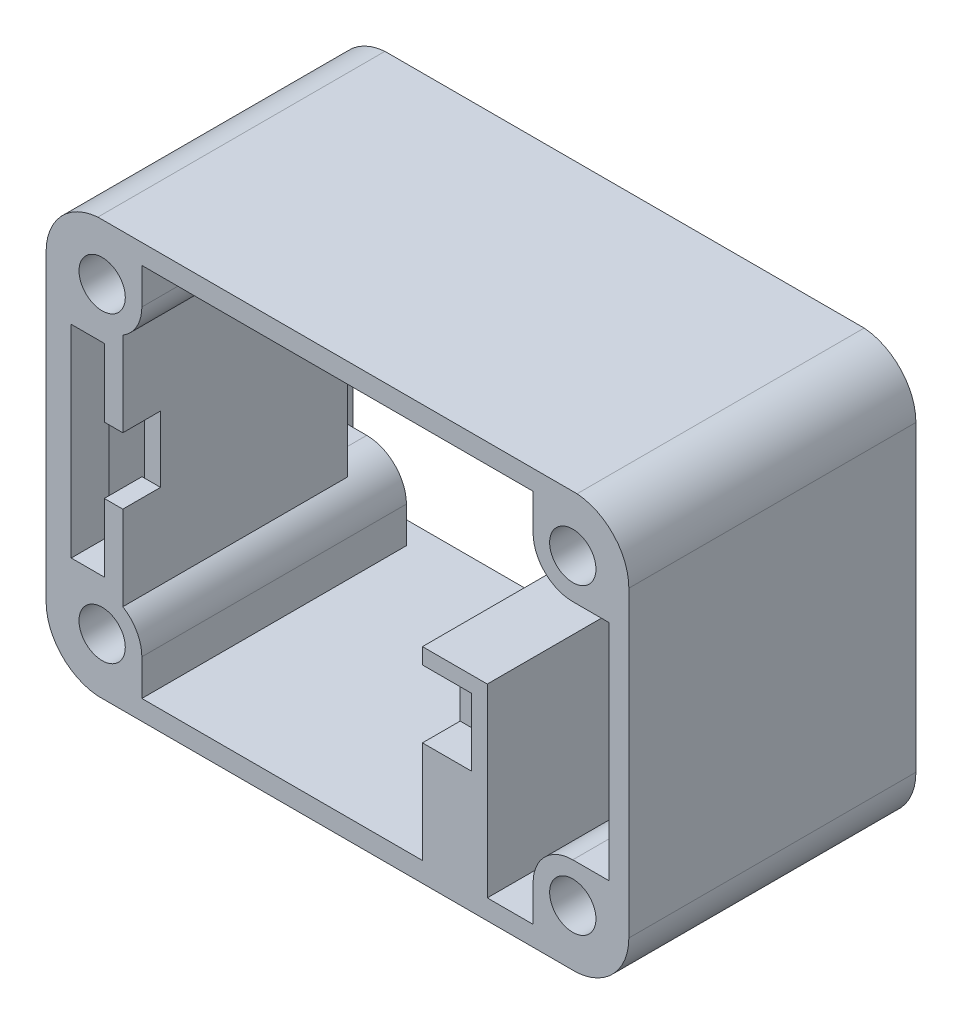
SolidWorks part; units mm, degrees
ref_plane "Front Plane" through (0, 0, 0) normal (0, 0, 1) x (1, 0, 0)
ref_plane "Top Plane" through (0, 0, 0) normal (0, 1, 0) x (1, 0, 0)
ref_plane "Right Plane" through (0, 0, 0) normal (1, 0, 0) x (0, 0, -1)
sketch "Sketch1" plane through (0, 0, 0) normal (0, 0, 1) x (1, 0, 0)
  line L0 (-20.325, 13.975) -> (-20.325, 14.175) construction
  line L1 (-22.025, -15.675) -> (22.025, -15.675)
  line L2 (-22.025, -15.675) -> (-22.025, 15.675)
  line L3 (-22.025, 15.675) -> (22.025, 15.675)
  line L4 (20.325, -13.975) -> (20.325, 13.975)
  line L5 (20.325, 13.975) -> (-20.325, 13.975)
  line L6 (-20.325, 13.975) -> (-20.325, -13.975)
  line L7 (-20.325, -13.975) -> (20.325, -13.975)
  line L8 (20.325, -13.975) -> (20.325, 13.975)
  line L9 (20.325, 13.975) -> (-20.325, 13.975)
  line L10 (-20.325, 13.975) -> (-20.325, -13.975)
  line L11 (-20.325, -13.975) -> (20.325, -13.975)
  line L12 (22.025, -15.675) -> (22.025, 15.675)
  line L13 (-22.025, -15.675) -> (22.025, 15.675) construction
  line L14 (-22.025, 15.675) -> (22.025, -15.675) construction
  line L15 (-20.325, 13.975) -> (-20.525, 13.975) construction
  line L16 (-14.7875, 11.45) -> (-14.7875, 14.175)
  line L17 (-17.7875, 8.45) -> (-20.525, 8.45)
  line L18 (0, 15.675) -> (0, -15.675) construction
  line L19 (-22.025, 0) -> (22.025, 0) construction
  line L20 (14.7875, 11.45) -> (14.7875, 14.175)
  line L21 (17.7875, 8.45) -> (20.525, 8.45)
  line L22 (17.7875, -8.45) -> (20.525, -8.45)
  line L23 (14.7875, -11.45) -> (14.7875, -14.175)
  line L24 (-14.7875, -11.45) -> (-14.7875, -14.175)
  line L25 (-17.7875, -8.45) -> (-20.525, -8.45)
  line L26 (-20.525, 14.175) -> (-22.025, 14.175) construction
  line L27 (20.525, -14.175) -> (-20.525, -14.175)
  line L28 (20.525, -14.175) -> (20.525, 14.175)
  line L29 (20.525, 14.175) -> (-20.525, 14.175)
  line L30 (-20.525, -14.175) -> (-20.525, 14.175)
  line L31 (20.525, -14.175) -> (-20.525, 14.175) construction
  line L32 (20.525, 14.175) -> (-20.525, -14.175) construction
  line L33 (-20.525, 14.175) -> (-20.525, 15.675) construction
  circle A0 centre (-17.7875, 11.45) radius 1.75
  circle A1 centre (17.7875, 11.45) radius 3
  circle A2 centre (17.7875, -11.45) radius 3
  circle A3 centre (-17.7875, -11.45) radius 3
  circle A4 centre (-17.7875, 11.45) radius 3
  circle A5 centre (17.7875, 11.45) radius 1.75
  circle A6 centre (17.7875, -11.45) radius 1.75
  circle A7 centre (-17.7875, -11.45) radius 1.75
  point P9 (0, 0)
  point P16 (0, 0)
  point P44 (-19.0562, -8.45)
  dimension "D2" = 3.5
  dimension "D4" = 6
  dimension "D3" = 1.5
  dimension "D5" = 0.2
  dimension "D1" = 0
extrude "Boss-Extrude1" add sketch "Sketch1" along normal blind 20 contours A4 L16 L9 | A4 L9 L16 L29 | L1 L12 L3 L2 A4 L29 A1 L28 A2 L27 A3 L30 | L29 A4 | A4 L29 L30 L10 L9 | A4 L9 L10 | L9 A4 L29 | L30 A4 | L10 A4 L30 | L9 A4 L10 A0 | A4 L30 L17 L10 | A4 L10 L17 | A1 L29 | L29 A1 L9 L8 L28 | L9 A1 L8 | A1 L8 L9 A5 | A1 L9 L29 | A1 L28 L8 | A1 L28 | L8 A1 L21 | L28 A1 L8 L21 | L20 A1 L9 | L9 A1 L29 L20 | A2 L28 L22 L8 | A2 L8 L22 | L8 A2 L11 A6 | L28 A2 | L28 A2 L8 | A2 L27 L28 L8 L11 | A2 L11 L8 | L11 A2 L27 | L27 A2 | A2 L23 L11 | A2 L11 L23 L27 | L27 A3 L11 L10 L30 | L11 A3 L10 | A3 L10 L30 | A3 L30 | L30 A3 L10 L25 | L10 A3 L25 | A3 L11 L10 A7 | A3 L11 L27 | A3 L27 | L24 A3 L11 | L11 A3 L27 L24 region at (-21.4843, 0, 0) region at (20.042, -13.6898, 0) region at (20.3461, -13.5127, 0) region at (19.8615, -13.508, 0) region at (20.4207, -11.45, 0) region at (17.7875, -14.0708, 0) region at (19.724, -8.8454, 0) region at (20.4289, -9.2415, 0) region at (20.6304, -11.45, 0) region at (15.5674, -14.0789, 0) region at (15.1778, -13.3764, 0) region at (17.7875, -14.2854, 0) region at (19.724, 8.8454, 0) region at (20.4289, 9.2415, 0) region at (-15.5674, -14.0789, 0) region at (-15.1778, -13.3764, 0) region at (19.1987, 8.8916, 0) region at (20.4207, 11.45, 0) region at (-17.7875, -14.0708, 0) region at (-17.7875, -13.8968, 0) region at (20.042, 13.6898, 0) region at (20.3461, 13.5127, 0) region at (20.6304, 11.45, 0) region at (15.1778, 13.3764, 0) region at (-19.2385, -14.0998, 0) region at (-20.042, -13.6898, 0) region at (-17.7875, -14.2854, 0) region at (-19.724, -8.8454, 0) region at (17.7875, 14.0708, 0) region at (15.5674, 14.0789, 0) region at (-20.4207, -11.45, 0) region at (-20.4289, -9.2415, 0) region at (17.7875, 14.2854, 0) region at (-15.1778, 13.3764, 0) region at (-15.5674, 14.0789, 0) region at (-20.6304, -11.45, 0) region at (-20.4289, 9.2415, 0) region at (-19.724, 8.8454, 0) region at (-15.2237, 12.8512, 0) region at (-17.7875, 14.0708, 0) region at (-20.4207, 11.45, 0) region at (-20.042, 13.6898, 0) region at (-19.8662, 13.9961, 0) region at (-17.7875, 14.2854, 0) region at (-20.6304, 11.45, 0)
sketch "Sketch2" plane through (0, 0, 0) normal (0, 0, -1) x (-1, 0, 0)
  line L0 (-14.7875, 14.175) -> (14.7875, 14.175) construction
  line L2 (-20.525, 14.175) -> (20.525, 14.175)
  line L3 (-20.525, 14.175) -> (-20.525, -14.175)
  line L4 (-20.525, -14.175) -> (20.525, -14.175)
  line L5 (-22.025, -15.675) -> (22.025, -15.675)
  line L6 (22.025, -15.675) -> (22.025, 15.675)
  line L7 (22.025, 15.675) -> (-22.025, 15.675)
  line L8 (-22.025, 15.675) -> (-22.025, -15.675)
  line L9 (-22.025, -15.675) -> (22.025, -15.675)
  line L10 (22.025, -15.675) -> (22.025, 15.675)
  line L11 (22.025, 15.675) -> (-22.025, 15.675)
  line L12 (-22.025, 15.675) -> (-22.025, -15.675)
  line L13 (20.525, 14.175) -> (20.525, -14.175)
  line L14 (-20.525, -8.45) -> (-20.525, 8.45) construction
  line L15 (20.525, -8.45) -> (20.525, 8.45) construction
  line L16 (-14.7875, -14.175) -> (14.7875, -14.175) construction
  line L17 (0, 14.175) -> (0, -14.175) construction
  line L18 (-20.525, 0) -> (20.525, 0) construction
  line L19 (2, -14.925) -> (2, -14.175)
  line L20 (-2, 14.925) -> (2, 14.925)
  line L21 (-2, 14.925) -> (-2, 14.175)
  line L22 (-2, 14.175) -> (2, 14.175)
  line L23 (2, 14.925) -> (2, 14.175)
  line L24 (-2, 14.925) -> (2, 14.175) construction
  line L25 (-2, 14.175) -> (2, 14.925) construction
  line L26 (-21.275, -2) -> (-20.525, -2)
  line L27 (-21.275, -2) -> (-21.275, 2)
  line L28 (-21.275, 2) -> (-20.525, 2)
  line L29 (-20.525, -2) -> (-20.525, 2)
  line L30 (-21.275, -2) -> (-20.525, 2) construction
  line L31 (-21.275, 2) -> (-20.525, -2) construction
  line L32 (-2, -14.925) -> (2, -14.925)
  line L33 (-2, -14.925) -> (-2, -14.175)
  line L34 (21.275, 2) -> (20.525, 2)
  line L35 (21.275, -2) -> (21.275, 2)
  line L36 (21.275, -2) -> (20.525, -2)
  point P20 (0, 14.55)
  point P25 (-20.9, 0)
  line M25 (-22.025, -15.675) -> (22.025, -15.675)
  line M26 (22.025, -15.675) -> (22.025, 15.675)
  line M27 (22.025, 15.675) -> (-22.025, 15.675)
  line M28 (-22.025, 15.675) -> (-22.025, -15.675)
  line M36 (20.525, 8.45) -> (20.525, -8.45)
  line M41 (-14.7875, 14.175) -> (14.7875, 14.175)
  line M62 (14.7875, -14.175) -> (-14.7875, -14.175)
  line M63 (-20.525, -8.45) -> (-20.525, 8.45)
  dimension "D2" = 0.75
  dimension "D3" = 4
  dimension "D1" = 0
extrude "Boss-Extrude2" add sketch "Sketch2" along normal blind 1.7 contours L35 L36 L13 L4 L19 L32 L33 L3 L26 L27 L28 L2 L21 L20 L23 L34 M28 M25 M26 M27 M36 M62 M63 M41 region at (21.4843, 0, 0)
ref_plane "Plane1" through (0, 0, 3) normal (0, 0, -1) x (-1, 0, 0)
sketch "Sketch3" plane through (0, 0, 3) normal (0, 0, -1) x (-1, 0, 0)
  line L0 (-20.525, 0) -> (20.525, 0) construction
  line L1 (-20.525, -2) -> (-20.525, 2) construction
  line L2 (20.525, -2) -> (20.525, 2) construction
  line L4 (-20.525, -8.45) -> (-20.525, 8.45) construction
  line L33 (20.525, 14.175) -> (20.525, 2) construction
  line L34 (16.225, -8.45) -> (20.525, -8.45)
  line L35 (16.225, -8.45) -> (16.225, 8.45)
  line L36 (16.225, 8.45) -> (20.525, 8.45)
  line L37 (20.525, -8.45) -> (20.525, 8.45)
  line L38 (16.225, -8.45) -> (20.525, 8.45) construction
  line L39 (16.225, 8.45) -> (20.525, -8.45) construction
  line L40 (17.7875, 8.45) -> (20.525, 8.45) construction
  line L41 (16.225, 8.45) -> (16.225, 8.889)
  line L42 (16.225, -8.45) -> (16.225, -8.889)
  line L43 (-8.875, 14.175) -> (-8.875, -14.175) construction
  line L44 (20.325, -7.85) -> (17.425, -7.85)
  line L45 (20.325, -7.85) -> (20.325, 7.85)
  line L46 (20.325, 7.85) -> (17.425, 7.85)
  line L47 (17.425, -7.85) -> (17.425, 7.85)
  line L48 (20.325, -7.85) -> (17.425, 7.85) construction
  line L49 (20.325, 7.85) -> (17.425, -7.85) construction
  line L50 (-20.525, 14.175) -> (-2, 14.175) construction
  line L51 (-2, -14.175) -> (-20.525, -14.175) construction
  line L52 (-10.325, -1.175) -> (-10.325, -0.175) construction
  line L53 (-6.425, -0.175) -> (-11.325, -0.175)
  line L54 (-6.425, -0.175) -> (-6.425, -14.175)
  line L55 (-6.425, -14.175) -> (-11.325, -14.175)
  line L56 (-11.325, -0.175) -> (-11.325, -14.175)
  line L57 (-6.425, -0.175) -> (-11.325, -14.175) construction
  line L58 (-6.425, -14.175) -> (-11.325, -0.175) construction
  line L59 (-10.325, -1.175) -> (-7.425, -1.175)
  line L60 (-10.325, -1.175) -> (-10.325, -6.675)
  line L61 (-10.325, -6.675) -> (-7.425, -6.675)
  line L62 (-7.425, -1.175) -> (-7.425, -6.675)
  line L63 (-10.325, -1.175) -> (-7.425, -6.675) construction
  line L64 (-10.325, -6.675) -> (-7.425, -1.175) construction
  line L65 (-10.325, -1.175) -> (-11.325, -1.175) construction
  arc A0 (-17.7875, 8.45) -> (-14.7875, 11.45) centre (-17.7875, 11.45) ccw construction
  arc A1 (-14.7875, -11.45) -> (-17.7875, -8.45) centre (-17.7875, -11.45) ccw construction
  arc A2 (-17.7875, 8.45) -> (-14.7875, 11.45) centre (-17.7875, 11.45) ccw
  arc A3 (-14.7875, -11.45) -> (-17.7875, -8.45) centre (-17.7875, -11.45) ccw
  arc A4 (14.7875, 11.45) -> (17.7875, 8.45) centre (17.7875, 11.45) ccw construction
  arc A5 (17.7875, -8.45) -> (14.7875, -11.45) centre (17.7875, -11.45) ccw construction
  arc A6 (17.7875, -8.45) -> (14.7875, -11.45) centre (17.7875, -11.45) ccw
  arc A7 (14.7875, 11.45) -> (17.7875, 8.45) centre (17.7875, 11.45) ccw
  point P41 (18.375, 0)
  point P58 (18.875, 0)
  point P71 (-8.875, -7.175)
  point P76 (-8.875, -3.925)
  dimension "D2" = 0.2
  dimension "D3" = 10.2
  dimension "D4" = 7.5
  dimension "D6" = 4.3
  dimension "D7" = 15.7
  dimension "D8" = 2.9
  dimension "D9" = 1
  dimension "D10" = 5.5
extrude "Boss-Extrude3" add sketch "Sketch3" against normal blind 14.15 contours A2 | A3 | L44 L47 L46 L37 L36 L35 L34 | A7 L41 L36 | A6 L34 L42 | L53 L56 L55 L54 L59 L62 L61 L60 region at (-16.3994, 0, 3) region at (-16.6097, -8.5799, 3) region at (-16.6097, 8.5799, 3) region at (8.875, -8.1596, 3)
sketch "Sketch4" plane through (0, 0, 17.15) normal (0, 0, 1) x (1, 0, 0)
  line L18 (11.325, -0.175) -> (6.425, -0.175)
  line L20 (-20.525, -8.45) -> (-17.7875, -8.45)
  line L21 (-16.225, -8.889) -> (-16.225, 8.889)
  line L22 (-17.7875, 8.45) -> (-20.525, 8.45)
  line L23 (-20.525, 8.45) -> (-20.525, -8.45)
  line L24 (-20.525, -8.45) -> (-17.7875, -8.45)
  line L25 (-16.225, -8.889) -> (-16.225, 8.889)
  line L26 (-17.7875, 8.45) -> (-20.525, 8.45)
  line L27 (-20.525, 8.45) -> (-20.525, -8.45)
  line L33 (-20.125, -7.65) -> (-17.625, -7.65)
  line L34 (-20.125, 7.65) -> (-20.125, -7.65)
  line L35 (11.325, -14.175) -> (11.325, -0.175)
  line L36 (6.425, -14.175) -> (11.325, -14.175)
  line L37 (6.425, -0.175) -> (6.425, -14.175)
  line L38 (11.325, -0.175) -> (6.425, -0.175)
  line L39 (11.325, -14.175) -> (11.325, -0.175)
  line L40 (6.425, -14.175) -> (11.325, -14.175)
  line L41 (6.425, -0.175) -> (6.425, -14.175)
  line L42 (-17.625, 7.65) -> (-20.125, 7.65)
  line L43 (-17.625, -7.65) -> (-17.625, 7.65)
  line L44 (-20.125, -7.65) -> (-17.625, -7.65)
  line L45 (-20.125, 7.65) -> (-20.125, -7.65)
  line L46 (7.625, -6.475) -> (10.125, -6.475)
  line L47 (7.625, -1.375) -> (7.625, -6.475)
  line L48 (10.125, -6.475) -> (10.125, -1.375)
  line L49 (10.125, -1.375) -> (7.625, -1.375)
  line L50 (7.625, -6.475) -> (10.125, -6.475)
  line L51 (7.625, -1.375) -> (7.625, -6.475)
  line L52 (10.125, -6.475) -> (10.125, -1.375)
  line L53 (10.125, -1.375) -> (7.625, -1.375)
  line L54 (-17.625, 7.65) -> (-20.125, 7.65)
  line L55 (-17.625, -7.65) -> (-17.625, 7.65)
  arc A2 (-16.225, -8.889) -> (-17.7875, -8.45) centre (-17.7875, -11.45) ccw
  arc A3 (-17.7875, 8.45) -> (-16.225, 8.889) centre (-17.7875, 11.45) ccw
  arc A4 (-16.225, -8.889) -> (-17.7875, -8.45) centre (-17.7875, -11.45) ccw
  arc A5 (-17.7875, 8.45) -> (-16.225, 8.889) centre (-17.7875, 11.45) ccw
  line M100 (-20.525, -8.45) -> (-17.7875, -8.45)
  arc M101 (-17.7875, -8.45) -> (-16.225, -8.889) centre (-17.7875, -11.45) cw
  line M102 (-16.225, -8.889) -> (-16.225, 8.889)
  arc M103 (-16.225, 8.889) -> (-17.7875, 8.45) centre (-17.7875, 11.45) cw
  line M104 (-17.7875, 8.45) -> (-20.525, 8.45)
  line M105 (-20.525, 8.45) -> (-20.525, -8.45)
  line M106 (-17.425, -7.85) -> (-20.325, -7.85)
  line M107 (-20.325, -7.85) -> (-20.325, 7.85)
  line M108 (-20.325, 7.85) -> (-17.425, 7.85)
  line M109 (-17.425, 7.85) -> (-17.425, -7.85)
  dimension "D1" = 0
  dimension "D2" = 0.2
  dimension "D3" = 0
  dimension "D4" = 0.2
extrude "Boss-Extrude4" add sketch "Sketch4" along normal up to surface (2.85 mm away) contours L38 L41 L40 L39 L53 L52 L50 L51 | M105 M100 M101 M102 M103 M104 M109 M106 M107 M108 | L55 L44 L45 L54 M106 M109 M108 M107 region at (8.875, -7.9169, 17.15) region at (-20.3421, 0, 17.15) region at (-18.875, -7.6903, 17.15) up to face at (0, 0, 20)
sketch "Sketch5" plane through (0, 0, 20) normal (0, 0, 1) x (1, 0, 0)
  line L0 (-16.225, 0) -> (-22.025, 0) construction
  line L1 (-16.225, -8.889) -> (-16.225, 8.889) construction
  line L2 (-22.025, -15.675) -> (-22.025, 15.675) construction
  line L3 (7.625, -3.925) -> (6.425, -3.925) construction
  line L4 (7.625, -1.375) -> (7.625, -6.475) construction
  line L5 (6.425, -0.175) -> (6.425, -14.175) construction
  line L6 (-17.625, -7.65) -> (-17.625, 7.65) construction
  line L7 (-17.625, -2.5) -> (-16.225, -2.5)
  line L8 (-17.625, -2.5) -> (-17.625, 2.5)
  line L9 (-17.625, 2.5) -> (-16.225, 2.5)
  line L10 (-16.225, -2.5) -> (-16.225, 2.5)
  line L11 (-17.625, -2.5) -> (-16.225, 2.5) construction
  line L12 (-17.625, 2.5) -> (-16.225, -2.5) construction
  line L14 (6.425, -6.475) -> (7.625, -6.475)
  line L15 (6.425, -6.475) -> (6.425, -1.375)
  line L16 (6.425, -1.375) -> (7.625, -1.375)
  line L17 (7.625, -6.475) -> (7.625, -1.375)
  line L18 (6.425, -6.475) -> (7.625, -1.375) construction
  line L19 (6.425, -1.375) -> (7.625, -6.475) construction
  point P12 (-16.925, 0)
  point P19 (7.025, -3.925)
  dimension "D1" = 5
extrude "Cut-Extrude1" cut sketch "Sketch5" against normal up to surface (2.85 mm away) up to face at (8.875, -3.925, 17.15)
sketch "Sketch6" plane through (0, 0, -1.7) normal (0, 0, -1) x (-1, 0, 0)
  line L5 (-22.025, 15.675) -> (-22.025, -15.675)
  line L6 (-22.025, -15.675) -> (22.025, -15.675)
  line L7 (22.025, -15.675) -> (22.025, 15.675)
  line L8 (22.025, 15.675) -> (-22.025, 15.675)
  line L9 (-22.025, 15.675) -> (-22.025, -15.675)
  line L10 (-22.025, -15.675) -> (22.025, -15.675)
  line L11 (22.025, -15.675) -> (22.025, 15.675)
  line L12 (22.025, 15.675) -> (-22.025, 15.675)
  circle A0 centre (-17.7875, 11.45) radius 4.2375
  circle A1 centre (17.7875, 11.45) radius 4.2375
  circle A2 centre (17.7875, -11.45) radius 4.2375
  circle A3 centre (-17.7875, -11.45) radius 4.2375
  line M5 (-22.025, 15.675) -> (-22.025, -15.675)
  line M6 (-22.025, -15.675) -> (22.025, -15.675)
  line M7 (22.025, -15.675) -> (22.025, 15.675)
  line M8 (22.025, 15.675) -> (-22.025, 15.675)
  dimension "D1" = 0
extrude "Cut-Extrude2" cut sketch "Sketch6" against normal up to next contours A0 M8 M5 | A1 L11 M8 | A2 M6 M7 | A3 M5 M6 region at (21.0925, 14.7286, -1.7) region at (21.0925, -14.7286, -1.7) region at (-21.0925, 14.7286, -1.7) region at (-21.0925, -14.7286, -1.7)
